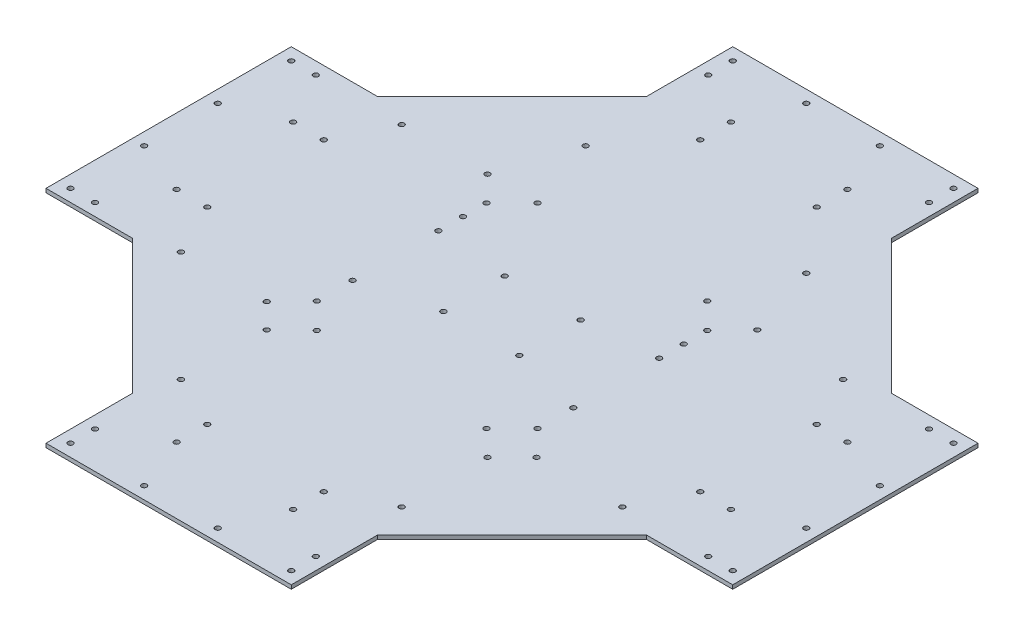
SolidWorks part; units mm, degrees
ref_plane "Front Plane" through (0, 0, 0) normal (0, 0, 1) x (1, 0, 0)
ref_plane "Top Plane" through (0, 0, 0) normal (0, 1, 0) x (1, 0, 0)
ref_plane "Right Plane" through (0, 0, 0) normal (1, 0, 0) x (0, 0, -1)
sketch "Sketch1" plane through (0, 0, 0) normal (0, 1, 0) x (1, 0, 0)
  line L0 (0, -280) -> (100, -280)
  line L1 (100, -280) -> (100, -209.6016)
  line L2 (280, -100) -> (209.6016, -100)
  line L3 (0, 0) -> (0, -280) construction
  line L4 (280, 0) -> (280, -100)
  line L5 (-280, 280) -> (280, 280) construction
  line L6 (-280, 280) -> (-280, -280) construction
  line L7 (-280, -280) -> (280, -280) construction
  line L8 (280, 280) -> (280, -280) construction
  line L9 (-280, 280) -> (280, -280) construction
  line L10 (-280, -280) -> (280, 280) construction
  line L11 (100, -209.6016) -> (209.6016, -100)
  line L12 (-280, 0) -> (-280, -100)
  line L13 (-280, -100) -> (-209.6016, -100)
  line L14 (-209.6016, -100) -> (-100, -209.6016)
  line L15 (-100, -280) -> (-100, -209.6016)
  line L16 (0, -280) -> (-100, -280)
  line L17 (0, 280) -> (-100, 280)
  line L18 (-100, 280) -> (-100, 209.6016)
  line L19 (-100, 209.6016) -> (-209.6016, 100)
  line L20 (-280, 100) -> (-209.6016, 100)
  line L21 (-280, 0) -> (-280, 100)
  line L22 (280, 0) -> (280, 100)
  line L23 (280, 100) -> (209.6016, 100)
  line L24 (209.6016, 100) -> (100, 209.6016)
  line L25 (100, 280) -> (100, 209.6016)
  line L26 (0, 280) -> (100, 280)
  line L27 (111.5258, -219.2889) -> (219.2889, -111.5258) construction
  line L28 (219.2889, -111.5258) -> (247.5732, -139.8101) construction
  line L29 (247.5732, -139.8101) -> (139.8101, -247.5732) construction
  line L30 (139.8101, -247.5732) -> (111.5258, -219.2889) construction
  line L31 (-100, -270) -> (100, -270) construction
  line L32 (-90, -280) -> (-90, 280) construction
  line L33 (-79.2, -79.2) -> (79.2, -79.2) construction
  line L34 (-79.2, -79.2) -> (-79.2, 79.2) construction
  line L35 (-79.2, 79.2) -> (79.2, 79.2) construction
  line L36 (79.2, -79.2) -> (79.2, 79.2) construction
  line L37 (-79.2, -79.2) -> (79.2, 79.2) construction
  line L38 (-79.2, 79.2) -> (79.2, -79.2) construction
  line L39 (-100, -260) -> (100, -260) construction
  line L40 (-280, 40) -> (280, 40) construction
  line L41 (0, 280) -> (0, 0) construction
  line L42 (-280, -90) -> (280, -90) construction
  line L43 (-260, -100) -> (-260, 100) construction
  line L44 (0, 0) -> (-280, 0) construction
  arc A0 (100, -280) -> (280, -100) centre (100, -100) ccw construction
  circle A1 centre (-47.5, -201) radius 2.125
  circle A2 centre (-47.5, -226) radius 2.125
  circle A3 centre (47.5, -226) radius 2.125
  circle A4 centre (47.5, -201) radius 2.125
  circle A5 centre (-201, 47.5) radius 2.125
  circle A6 centre (-226, 47.5) radius 2.125
  circle A7 centre (-201, -47.5) radius 2.125
  circle A8 centre (-226, -47.5) radius 2.125
  circle A9 centre (47.5, 201) radius 2.125
  circle A10 centre (47.5, 226) radius 2.125
  circle A11 centre (-47.5, 201) radius 2.125
  circle A12 centre (-47.5, 226) radius 2.125
  circle A13 centre (201, -47.5) radius 2.125
  circle A14 centre (226, -47.5) radius 2.125
  circle A15 centre (201, 47.5) radius 2.125
  circle A16 centre (226, 47.5) radius 2.125
  circle A17 centre (-90, -270) radius 2.125
  circle A18 centre (-30, -270) radius 2.125
  circle A19 centre (30, -270) radius 2.125
  circle A20 centre (90, -270) radius 2.125
  circle A21 centre (-270, 90) radius 2.125
  circle A22 centre (-270, 30) radius 2.125
  circle A23 centre (-270, -30) radius 2.125
  circle A24 centre (-270, -90) radius 2.125
  circle A25 centre (90, 270) radius 2.125
  circle A26 centre (30, 270) radius 2.125
  circle A27 centre (-30, 270) radius 2.125
  circle A28 centre (-90, 270) radius 2.125
  circle A29 centre (270, -90) radius 2.125
  circle A30 centre (270, -30) radius 2.125
  circle A31 centre (270, 30) radius 2.125
  circle A32 centre (270, 90) radius 2.125
  circle A33 centre (-90, -250) radius 2.125
  circle A34 centre (-90, -180) radius 2.125
  circle A35 centre (-90, -110) radius 2.125
  circle A36 centre (-90, -40) radius 2.125
  circle A37 centre (-90, 30) radius 2.125
  circle A38 centre (-90, 50) radius 2.125
  circle A39 centre (-90, 100) radius 2.125 construction
  circle A40 centre (-90, 150) radius 2.125
  circle A41 centre (-90, 200) radius 2.125 construction
  circle A42 centre (-90, 250) radius 2.125
  circle A43 centre (90, -250) radius 2.125
  circle A44 centre (90, -180) radius 2.125
  circle A45 centre (90, -110) radius 2.125
  circle A46 centre (90, -40) radius 2.125
  circle A47 centre (90, 30) radius 2.125
  circle A48 centre (90, 50) radius 2.125
  circle A49 centre (90, 100) radius 2.125 construction
  circle A50 centre (90, 150) radius 2.125
  circle A51 centre (90, 200) radius 2.125 construction
  circle A52 centre (90, 250) radius 2.125
  circle A53 centre (-250, -90) radius 2.125
  circle A54 centre (-180, -90) radius 2.125
  circle A55 centre (-110, -90) radius 2.125
  circle A56 centre (-110, 90) radius 2.125
  circle A57 centre (-180, 90) radius 2.125
  circle A58 centre (-250, 90) radius 2.125
  circle A59 centre (110, -90) radius 2.125
  circle A60 centre (180, -90) radius 2.125
  circle A61 centre (250, -90) radius 2.125
  circle A62 centre (110, 90) radius 2.125
  circle A63 centre (180, 90) radius 2.125
  circle A64 centre (250, 90) radius 2.125
  point P33 (0, 0)
  point P68 (0, 0)
  point P107 (0, 0)
  dimension "D10" = 25
  dimension "4.25" = 4.25
  dimension "D11" = 4.25
  dimension "D16" = 4.25
  dimension "D24" = 4.25
  dimension "D28" = 4.25
  dimension "D32" = 4.25
  dimension "D1" = 560
  dimension "D2" = 90
  dimension "D3" = 280
  dimension "D4" = 4
  dimension "D5" = 100
  dimension "D6" = 155
  dimension "D7" = 152.4
  dimension "D8" = 15
  dimension "D9" = 40
  dimension "D12" = 47.5
  dimension "D13" = 54
  dimension "D15" = 10
  dimension "D17" = 10
  dimension "D18" = 76.2
  dimension "D19" = 158.4
  dimension "D20" = 158.4
  dimension "D23" = 10
  dimension "D25" = 10
  dimension "D26" = 300
  dimension "D29" = 10
  dimension "D31" = 20
  dimension "D33" = 10
  dimension "D21" = 4
  dimension "D27" = 5
  dimension "D30" = 5
  dimension "D34" = 3
  dimension "D14" = 4
  dimension "D22" = 4
extrude "Boss-Extrude1" add sketch "Sketch1" along normal blind 3.175 contours L26 L17 L18 L19 L20 L21 L12 L13 L14 L15 L16 L0 L1 L11 L2 L4 L22 L23 L24 L25 region at (0, 0, -0.0137)
sketch "Sketch2" plane through (0, 3.175, 0) normal (0, 1, 0) x (1, 0, 0)
  line L0 (0, 25.5202) -> (0, -25) construction
  line L1 (-31, -25) -> (31, -25) construction
  line L2 (-31, -25) -> (-31, 25) construction
  line L3 (-31, 25) -> (31, 25) construction
  line L4 (31, -25) -> (31, 25) construction
  line L5 (-31, -25) -> (31, 25) construction
  line L6 (-31, 25) -> (31, -25) construction
  line L7 (79.2, -79.2) -> (79.2, 79.2) construction
  line L8 (-79.2, -79.2) -> (79.2, -79.2) construction
  line L9 (-79.2, -79.2) -> (-79.2, 79.2) construction
  line L10 (-79.2, 79.2) -> (79.2, 79.2) construction
  line L11 (79.2, -79.2) -> (79.2, 79.2) construction
  line L12 (-79.2, -79.2) -> (79.2, -79.2) construction
  line L13 (-79.2, -79.2) -> (-79.2, 79.2) construction
  line L14 (-79.2, 79.2) -> (79.2, 79.2) construction
  line L15 (-90, 270) -> (-90, -270) construction
  line L16 (-270, 90) -> (270, 90) construction
  circle A0 centre (-31, 25) radius 2.125
  circle A1 centre (-31, -25) radius 2.125
  circle A2 centre (31, -25) radius 2.125
  circle A3 centre (31, 25) radius 2.125
  circle A4 centre (-90, 69.2) radius 2.125
  circle A5 centre (-69.2, 90) radius 2.125
  circle A6 centre (69.2, 90) radius 2.125
  circle A7 centre (90, 69.2) radius 2.125
  circle A8 centre (90, -69.2) radius 2.125
  circle A9 centre (69.2, -90) radius 2.125
  circle A10 centre (-69.2, -90) radius 2.125
  circle A11 centre (-90, -69.2) radius 2.125
  point P0 (0, 0)
  point P28 (0, 0)
  point P43 (0, 0)
  dimension "D3" = 4.25
  dimension "D4" = 4.25
  dimension "D5" = 4.25
  dimension "D7" = 4.25
  dimension "D1" = 62
  dimension "D2" = 50
  dimension "D6" = 10
  dimension "D8" = 10
  dimension "D9" = 4
extrude "Cut-Extrude1" cut sketch "Sketch2" against normal through all
